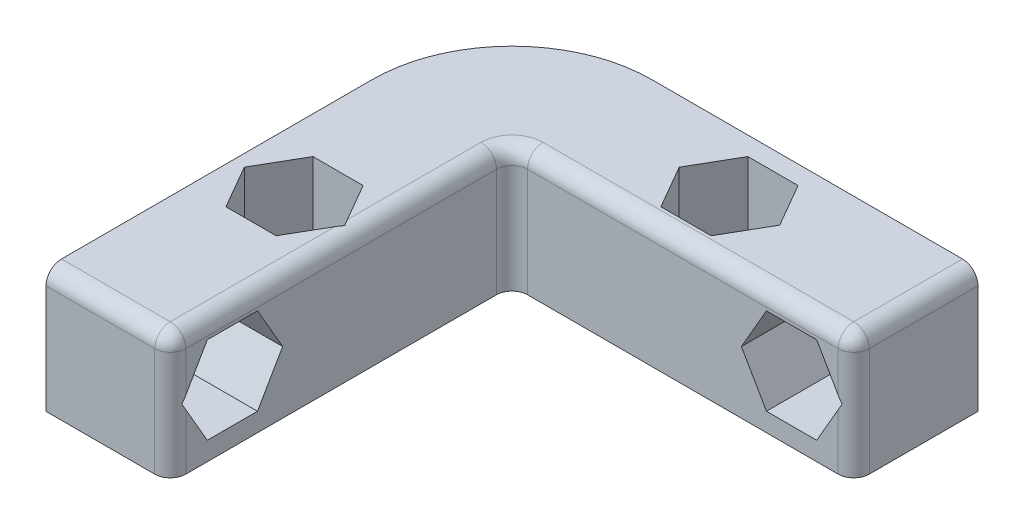
SolidWorks part; units mm, degrees
ref_plane "Plan de face" through (0, 0, 0) normal (0, 0, 1) x (1, 0, 0)
ref_plane "Plan de dessus" through (0, 0, 0) normal (0, 1, 0) x (1, 0, 0)
ref_plane "Plan de droite" through (0, 0, 0) normal (1, 0, 0) x (0, 0, -1)
sketch "Esquisse1" plane through (0, 0, 0) normal (0, 1, 0) x (1, 0, 0)
  line L0 (30, 0) -> (9, 0)
  line L1 (0, -9) -> (0, -30)
  arc A0 (9, 0) -> (0, -9) centre (9, -9) ccw
  point P6 (0, 0)
  dimension "D1" = 9
  dimension "D2" = 30
extrude "Extru.-Mince1" add sketch "Esquisse1" along normal blind 8 thin thin type one direction reverse wall 8
sketch "Esquisse2" plane through (0, 0, 0) normal (0, -1, 0) x (1, 0, 0)
  line L0 (30, 4) -> (18, 4) construction
  line L1 (30, 0) -> (30, 8) construction
  line L3 (8, 30) -> (0, 30) construction
  line L4 (4, 30) -> (4, 18) construction
  circle A0 centre (18, 4) radius 1.6
  circle A1 centre (4, 18) radius 1.6
  dimension "D1" = 3.2
  dimension "D2" = 12
extrude "Enlèv. mat.-Extru.1" cut sketch "Esquisse2" against normal up to next
sketch "Esquisse3" plane through (0, 8, 0) normal (0, 1, 0) x (1, 0, 0)
  line L1 (5.6166, -20.8) -> (7.2332, -18)
  line L2 (7.2332, -18) -> (5.6166, -15.2)
  line L3 (5.6166, -15.2) -> (2.3834, -15.2)
  line L4 (2.3834, -15.2) -> (0.7668, -18)
  line L5 (0.7668, -18) -> (2.3834, -20.8)
  line L6 (2.3834, -20.8) -> (5.6166, -20.8)
  line L7 (19.6166, -6.8) -> (21.2332, -4)
  line L8 (21.2332, -4) -> (19.6166, -1.2)
  line L9 (19.6166, -1.2) -> (16.3834, -1.2)
  line L10 (16.3834, -1.2) -> (14.7668, -4)
  line L11 (14.7668, -4) -> (16.3834, -6.8)
  line L12 (16.3834, -6.8) -> (19.6166, -6.8)
  circle A2 centre (4, -18) radius 2.8 construction
  circle A3 centre (18, -4) radius 2.8 construction
  dimension "D1" = 5.6
  dimension "D2" = 5.6
extrude "Enlèv. mat.-Extru.2" cut sketch "Esquisse3" against normal blind 5.5
sketch "Esquisse4" plane through (0, 0, 0) normal (0, 0, -1) x (-1, 0, 0)
  line L0 (-30, 4) -> (-26, 4) construction
  line L1 (-30, 8) -> (-30, 0) construction
  circle A0 centre (-26, 4) radius 1.6
  dimension "D2" = 3.2
  dimension "D1" = 4
extrude "Enlèv. mat.-Extru.3" cut sketch "Esquisse4" against normal up to next
sketch "Esquisse5" plane through (0, 0, 8) normal (0, 0, 1) x (1, 0, 0)
  line L1 (27.6166, 1.2) -> (29.2332, 4)
  line L2 (29.2332, 4) -> (27.6166, 6.8)
  line L3 (27.6166, 6.8) -> (24.3834, 6.8)
  line L4 (24.3834, 6.8) -> (22.7668, 4)
  line L5 (22.7668, 4) -> (24.3834, 1.2)
  line L6 (24.3834, 1.2) -> (27.6166, 1.2)
  circle A1 centre (26, 4) radius 2.8 construction
extrude "Enlèv. mat.-Extru.4" cut sketch "Esquisse5" against normal blind 5.5
ref_plane "Plan1" through (0, 0, 0) normal (0.7071, 0, -0.7071) x (-0.7071, 0, -0.7071)
mirror "Symétrie1" about plane through (0, 0, 0) normal (0.7071, 0, -0.7071) of "Enlèv. mat.-Extru.4", "Enlèv. mat.-Extru.3"
fillet "Congé1" radius 1 7 edges at (19.5, 8, 8) (8.2929, 8, 8.2929) (8, 4, 30) (4, 8, 30) (8, 8, 19.5) (30, 4, 8) (30, 8, 4)
